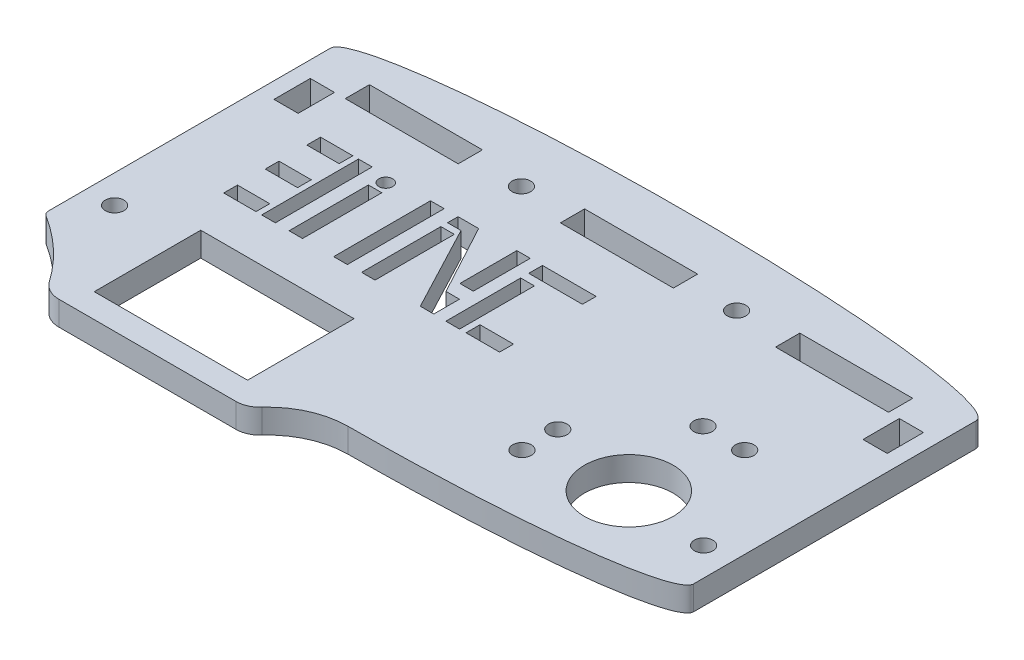
SolidWorks part; units mm, degrees
ref_plane "Front Plane" through (0, 0, 0) normal (0, 0, 1) x (1, 0, 0)
ref_plane "Top Plane" through (0, 0, 0) normal (0, 1, 0) x (1, 0, 0)
ref_plane "Right Plane" through (0, 0, 0) normal (1, 0, 0) x (0, 0, -1)
sketch "Sketch1" plane through (0, 0, 0) normal (0, 1, 0) x (1, 0, 0)
  line L1 (40, 17.5) -> (-40, 17.5)
  line L2 (40, 17.5) -> (40, -17.5)
  line L3 (40, -17.5) -> (-40, -17.5)
  line L4 (-40, 17.5) -> (-40, -17.5)
  line L5 (40, 17.5) -> (-40, -17.5) construction
  line L6 (40, -17.5) -> (-40, 17.5) construction
  point P0 (0, 0)
  dimension "D1" = 35
  dimension "D2" = 80
extrude "Boss-Extrude1" add sketch "Sketch1" along normal mid plane 3
sketch "Sketch2" plane through (0, 1.5, 0) normal (0, 1, 0) x (1, 0, 0)
  line L0 (-33.6667, 16) -> (-33.6667, 13) construction
  line L1 (-19.6667, 16) -> (-33.6667, 16) construction
  line L2 (-33.6667, 13) -> (-19.6667, 13) construction
  line L3 (-19.6667, 13) -> (-19.6667, 16) construction
  line L4 (-7, 16) -> (-7, 13) construction
  line L5 (7, 16) -> (-7, 16) construction
  line L6 (-7, 13) -> (7, 13) construction
  line L7 (7, 13) -> (7, 16) construction
  line L8 (19.6667, 16) -> (19.6667, 13) construction
  line L9 (33.6667, 16) -> (19.6667, 16) construction
  line L10 (19.6667, 13) -> (33.6667, 13) construction
  line L11 (33.6667, 13) -> (33.6667, 16) construction
  line L12 (-33.6667, 16) -> (-33.6667, 13)
  line L13 (-19.6667, 16) -> (-33.6667, 16)
  line L14 (-33.6667, 13) -> (-19.6667, 13)
  line L15 (-19.6667, 13) -> (-19.6667, 16)
  line L16 (-7, 16) -> (-7, 13)
  line L17 (7, 16) -> (-7, 16)
  line L18 (-7, 13) -> (7, 13)
  line L19 (7, 13) -> (7, 16)
  line L20 (19.6667, 16) -> (19.6667, 13)
  line L21 (33.6667, 16) -> (19.6667, 16)
  line L22 (19.6667, 13) -> (33.6667, 13)
  line L23 (33.6667, 13) -> (33.6667, 16)
  circle A0 centre (-13.3333, 14.5) radius 1.15 construction
  circle A1 centre (13.3333, 14.5) radius 1.15 construction
  circle A2 centre (-13.3333, 14.5) radius 1.15
  circle A3 centre (13.3333, 14.5) radius 1.15
extrude "Cut-Extrude1" cut sketch "Sketch2" against normal through all
sketch "Sketch3" plane through (0, 1.5, 0) normal (0, 1, 0) x (1, 0, 0)
  line L0 (40, 17.5) -> (-40, 17.5) construction
  line L1 (40, 17.5) -> (-40, 17.5)
  ellipse E0 centre (0, 17.5) end of major axis (-40, 17.5) minor radius 4.5 (40, 17.5) -> (-40, 17.5) ccw
  dimension "D1" = 4.5
extrude "Boss-Extrude2" add sketch "Sketch3" against normal up to vertex (3 mm away) up to point (40, -1.5, -17.5)
sketch "Sketch7" plane through (0, -1.5, 0) normal (0, -1, 0) x (1, 0, 0)
  line L0 (-36.5, 11.6) -> (-36.5, 13.9) construction
  line L1 (35, -8.5) -> (38, -8.5)
  line L2 (35, -8.5) -> (35, -13)
  line L3 (35, -13) -> (38, -13)
  line L4 (38, -8.5) -> (38, -13)
  line L5 (-35, -8.5) -> (-38, -8.5)
  line L6 (-35, -8.5) -> (-35, -13)
  line L7 (-35, -13) -> (-38, -13)
  line L8 (-38, -8.5) -> (-38, -13)
  line L9 (-35, 11.6) -> (-38, 11.6) construction
  line L10 (-35, 13.9) -> (-38, 13.9) construction
  line L11 (36.5, 13.9) -> (36.5, 11.6) construction
  line L12 (38, 13.9) -> (35, 13.9) construction
  line L13 (38, 11.6) -> (35, 11.6) construction
  circle A0 centre (-36.5, 12.75) radius 1.15
  circle A1 centre (36.5, 12.75) radius 1.15
extrude "Cut-Extrude3" cut sketch "Sketch7" against normal through all
sketch "Sketch8" plane through (0, -1.5, 0) normal (0, -1, 0) x (1, 0, 0)
  line L0 (-40, 17.5) -> (40, 17.5) construction
  line L1 (-40, 17.5) -> (40, 17.5)
  ellipse E0 centre (0, 17.5) end of major axis (40, 17.5) minor radius 4.5 (40, 17.5) -> (-40, 17.5) ccw
  dimension "D1" = 4.5
extrude "Boss-Extrude3" add sketch "Sketch8" against normal up to vertex (3 mm away) up to point (40, 1.5, 17.5)
sketch "Sketch10" plane through (0, 1.5, 0) normal (0, 1, 0) x (1, 0, 0)
  line L0 (-31.5, -20.2734) -> (-31.5, -26.2734)
  line L1 (-28.5, -10.0734) -> (-9.5, -10.0734)
  line L2 (-28.5, -10.0734) -> (-28.5, -23.2734)
  line L3 (-28.5, -23.2734) -> (-9.5, -23.2734)
  line L4 (-9.5, -10.0734) -> (-9.5, -23.2734)
  line L5 (-28.5, -10.0734) -> (-9.5, -23.2734) construction
  line L6 (-28.5, -23.2734) -> (-9.5, -10.0734) construction
  line L7 (-31.5, -26.2734) -> (-6.5, -26.2734)
  line L8 (-6.5, -26.2734) -> (-6.5, -21.9402)
  line L9 (-9.5, -23.2734) -> (-6.5, -23.2734) construction
  line L10 (-9.5, -23.2734) -> (-9.5, -26.2734) construction
  line L11 (-28.5, -23.2734) -> (-31.5, -23.2734) construction
  line L12 (-31.5, -12.75) -> (-31.5, -20.2734) construction
  line L13 (-36.5, -12.75) -> (-31.5, -12.75) construction
  ellipse E0 centre (0, -17.5) end of major axis (40, -17.5) minor radius 4.5 (-40, -17.5) -> (40, -17.5) ccw construction
  ellipse E1 centre (0, -17.5) end of major axis (40, -17.5) minor radius 4.5 (-31.5, -20.2734) -> (-6.5, -21.9402) ccw
  point P0 (-19, -16.6734)
  ellipse M32 centre (0, -17.5) end of major axis (40, -17.5) minor radius 4.5 (-40, -17.5) -> (40, -17.5) ccw
  dimension "D1" = 19
  dimension "D2" = 13.2
  dimension "D3" = 3
  dimension "D4" = 5
extrude "Boss-Extrude4" add sketch "Sketch10" against normal up to vertex (3 mm away) contours L7 L8 L4 L3 L2 L0 M32 | L4 L2 L3 M32 region at (-19.5451, 1.5, 24.3925) region at (-20.0025, 1.5, 22.3025) up to point (40, -1.5, 17.5)
extrude "Cut-Extrude4" cut sketch "Sketch10<3>" against normal blind 10 contours L4 L1 L2 M32 | L4 L2 L3 M32 region at (-20.0025, 1.5, 22.3025) region at (-18.8338, 1.5, 15.7401)
sketch "Sketch10<3>" plane through (0, 1.5, 0) normal (0, 1, 0) x (1, 0, 0) same geometry as "Sketch10"
fillet "Fillet1" radius 25 1 edges
fillet "Fillet2" radius 10 1 edges
fillet "Fillet3" radius 3 2 edges at (-31.5, 0, 26.2734) (-6.5, 0, 26.2734)
sketch "Sketch14" plane through (0, 1.5, 0) normal (0, 1, 0) x (1, 0, 0)
  line L21 (-5.061, -4.6334) -> (-3.561, -4.6334) construction
  line L66 (-26.3622, 7.337) -> (-24.6622, 7.337)
  line L67 (-26.3622, 7.337) -> (-26.3622, -4.663)
  line L68 (-26.3622, -4.663) -> (-24.6622, -4.663)
  line L69 (-24.6622, 7.337) -> (-24.6622, -4.663)
  line L70 (-27.0636, 2.1861) -> (-31.0636, 2.1861)
  line L71 (-27.0624, 7.337) -> (-31.0624, 7.337)
  line L72 (-27.0624, 7.337) -> (-27.0624, 5.637)
  line L73 (-27.0624, 5.637) -> (-31.0624, 5.637)
  line L74 (-31.0624, 7.337) -> (-31.0624, 5.637)
  line L75 (-27.0636, 2.1861) -> (-27.0636, 0.4861)
  line L76 (-27.0636, 0.4861) -> (-31.0636, 0.4861)
  line L77 (-31.0636, 2.1861) -> (-31.0636, 0.4861)
  line L78 (-27.0676, -2.9559) -> (-31.0676, -2.9559)
  line L79 (-27.0676, -2.9559) -> (-27.0676, -4.6559)
  line L80 (-27.0676, -4.6559) -> (-31.0676, -4.6559)
  line L81 (-31.0676, -2.9559) -> (-31.0676, -4.6559)
  line L82 (-3.5453, 4.6209) -> (-1.8453, 4.6209)
  line L83 (-3.5453, 4.6209) -> (-3.5453, -4.6554)
  line L84 (-3.5453, -4.6554) -> (-1.8453, -4.6554)
  line L85 (-1.8453, 4.6209) -> (-1.8453, -4.6554)
  line L86 (-22.9655, 5.165) -> (-21.2968, 5.165)
  line L87 (-22.9655, 5.165) -> (-22.9655, -4.6614)
  line L88 (-22.9655, -4.6614) -> (-21.2968, -4.6614)
  line L89 (-21.2968, 5.165) -> (-21.2968, -4.6614)
  line L90 (-3.5453, 7.3187) -> (3.1058, 7.3187)
  line L91 (-3.5453, 7.3187) -> (-3.5453, 5.6187)
  line L92 (-17.4242, 7.3224) -> (-15.7242, 7.3224)
  line L93 (-17.4242, 7.3224) -> (-17.4242, -4.6776)
  line L94 (-17.4242, -4.6776) -> (-15.7242, -4.6776)
  line L95 (-15.7242, 7.3224) -> (-15.7242, -4.6776)
  line L96 (-3.5453, 5.6187) -> (3.1058, 5.6187)
  line L97 (3.1058, 7.3187) -> (3.1058, 5.6187)
  line L98 (-1.047, -2.918) -> (3.1058, -2.918)
  line L99 (-1.047, -2.918) -> (-1.047, -4.6451)
  line L100 (-1.047, -4.6451) -> (3.1058, -4.6451)
  line L101 (-14.0079, 5.193) -> (-12.3391, 5.193)
  line L102 (-14.0079, 5.193) -> (-14.0079, -4.6334)
  line L103 (-14.0079, -4.6334) -> (-12.3391, -4.6334)
  line L104 (-12.3391, 5.193) -> (-12.3391, -4.6334)
  line L105 (3.1058, -2.918) -> (3.1058, -4.6451)
  line L106 (-14.0079, 7.3224) -> (-14.0079, 6.0193)
  line L107 (-14.0079, 6.0193) -> (-12.3391, 6.0193)
  line L108 (-12.3391, 6.0193) -> (-6.7297, -4.6334)
  line L109 (-6.7297, -4.6334) -> (-5.061, -4.6334)
  line L110 (-14.0079, 7.3224) -> (-11.4573, 7.3224)
  line L111 (-11.4573, 7.3224) -> (-6.7297, -1.4496)
  line L112 (-6.7297, -1.4496) -> (-5.061, -1.4496)
  line L113 (-5.061, -1.4496) -> (-5.061, -4.6334)
  line L114 (-6.7217, 7.3224) -> (-6.7217, 0.2667)
  line L115 (-6.7217, 0.2667) -> (-5.061, 0.2667)
  line L116 (-5.061, 0.2667) -> (-5.061, 7.3224)
  line L117 (-5.061, 7.3224) -> (-6.7217, 7.3224)
  circle A2 centre (-22.1311, 6.487) radius 0.85
  circle A3 centre (-22.1311, 6.487) radius 0.85
extrude "Cut-Extrude7" cut sketch "Sketch14" against normal blind 10 contours L71 L74 L73 L72 | L70 L77 L76 L75 | L78 L81 L80 L79 | L69 L66 L67 L68 | L89 L86 L87 L88 | L95 L92 L93 L94 | L104 L101 L102 L103 | L113 L112 L111 L110 L106 L107 L108 L109 | L116 L117 L114 L115 | L85 L82 L83 L84 | L97 L90 L91 L96 | L105 L98 L99 L100 | A2 region at (-25.5122, 1.5, -1.337) region at (-29.0636, 1.5, -1.3361) region at (-29.0624, 1.5, -6.487) region at (-29.0676, 1.5, 3.8059) region at (-2.6953, 1.5, 0.0172) region at (-22.1311, 1.5, -0.2518) region at (-0.2197, 1.5, -6.4687) region at (-16.5742, 1.5, -1.3224) region at (1.0294, 1.5, 3.7816) region at (-13.1735, 1.5, -0.2798) region at (-8.9549, 1.5, -1.2388) region at (-5.8913, 1.5, -3.7945)
sketch "Sketch16" plane through (0, 1.5, 0) normal (0, 1, 0) x (1, 0, 0)
  line L1 (6.2857, -6.5193) -> (16.2857, -6.5193)
  line L2 (6.2857, -6.5193) -> (6.2857, -16.5193)
  line L3 (6.2857, -16.5193) -> (16.2857, -16.5193)
  line L4 (16.2857, -6.5193) -> (16.2857, -16.5193)
  circle A4 centre (25.9967, -11.5193) radius 5.5
  circle A5 centre (25.9967, -11.5193) radius 5.5
extrude "Cut-Extrude8" cut sketch "Sketch16" against normal blind 10 contours A4 | A4 region at (25.9967, 1.5, 11.5193)
sketch "Sketch17" plane through (0, 1.5, 0) normal (0, 1, 0) x (1, 0, 0)
  circle A0 centre (15.0078, -13.7706) radius 1.15
  circle A1 centre (23.6625, 0) radius 1.15
  circle A2 centre (28.8098, 0.0253) radius 1.15
  circle A3 centre (15.0014, -9.3291) radius 1.15
  point P4 (0, 0)
  point P15 (0, 0)
extrude "Cut-Extrude9" cut sketch "Sketch17" against normal blind 10 contours A3 | A1 | A2 | A0
